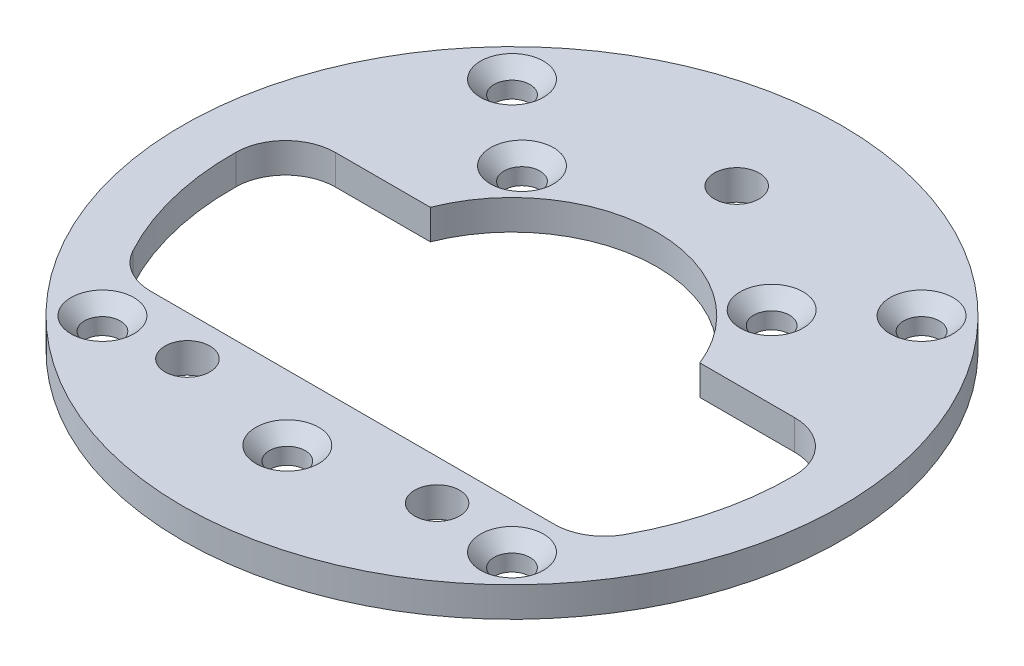
SolidWorks part; units mm, degrees
material "ABS"
ref_plane "Front Plane" through (0, 0, 0) normal (0, 0, 1) x (1, 0, 0)
ref_plane "Top Plane" through (0, 0, 0) normal (0, 1, 0) x (1, 0, 0)
ref_plane "Right Plane" through (0, 0, 0) normal (1, 0, 0) x (0, 0, -1)
sketch "Sketch1" plane through (0, 0, 0) normal (0, 1, 0) x (1, 0, 0)
  circle A0 centre (0, 0) radius 33
  circle A1 centre (0, 0) radius 28
  dimension "D1" = 66
  dimension "D2" = 5
extrude "Boss-Extrude1" add sketch "Sketch1" along normal blind 3
sketch "Sketch2" plane through (0, 3, 0) normal (0, 1, 0) x (1, 0, 0)
  line L0 (-23, -15.9687) -> (23, -15.9687)
  line L1 (-27.4911, 5.3142) -> (-13.4911, 5.3142)
  line L2 (0, 0) -> (7.7557, 0) construction
  line L3 (13.4911, 5.3142) -> (27.4911, 5.3142)
  line L4 (-20.5061, 20.5061) -> (0, 0) construction
  line L5 (-12.5, 13.5) -> (12.5, 13.5) construction
  circle A0 centre (0, 22.5) radius 2.25 construction
  circle A1 centre (-12.5, -20) radius 2.25 construction
  circle A2 centre (12.5, -20) radius 2.25 construction
  circle A4 centre (-12.5, 13.5) radius 1.5
  circle A6 centre (0, 0) radius 28 construction
  arc A8 (-13.4911, 5.3142) -> (13.4911, 5.3142) centre (0, 0) cw
  arc A9 (27.4911, 5.3142) -> (-27.4911, 5.3142) centre (0, 0) ccw
  arc A10 (23, -15.9687) -> (-23, -15.9687) centre (0, 0) cw
  circle A11 centre (12.5, 13.5) radius 1.5
  circle A12 centre (0, 0) radius 29 construction
  circle A13 centre (0, 0) radius 33 construction
  circle A14 centre (-20.5061, 20.5061) radius 1.75 construction
  circle A15 centre (20.5061, 20.5061) radius 1.75 construction
  circle A16 centre (20.5061, -20.5061) radius 1.75 construction
  circle A17 centre (-20.5061, -20.5061) radius 1.75 construction
  circle A18 centre (0, -22.5) radius 1.5
  point P15 (0, 13.5)
  point P19 (0, 0)
  point P44 (0, 0)
  circle M2 centre (0, 0) radius 28
  dimension "D5" = 4.5
  dimension "D6" = 4.5
  dimension "D7" = 4.5
  dimension "D12" = 14.5
  dimension "D16" = 3.5
  dimension "D11" = 3
  dimension "D1" = 25
  dimension "D2" = 12.5
  dimension "D3" = 22.5
  dimension "D4" = 20
  dimension "D14" = 4
  dimension "D15" = 135
  dimension "D8" = 14
  dimension "D9" = 14
  dimension "D10" = 46
  dimension "D13" = 36
  dimension "D18" = 25
  dimension "D19" = 22.5
  dimension "D17" = 4
extrude "Saliente-Extruir1" add sketch "Sketch2" against normal up to surface (3 mm away) contours L1 A8 L3 M2 | L0 M2 region at (0, 3, 20.8526) region at (0, 3, -16.2061) up to face at (0, 0, 33)
sketch "Croquis1" plane through (0, 3, 0) normal (0, 1, 0) x (1, 0, 0)
  circle A0 centre (-20.5061, 20.5061) radius 1.75 construction
  circle A1 centre (-20.5061, 20.5061) radius 1.75
  circle A2 centre (0, 22.5) radius 2.25 construction
  circle A3 centre (0, 22.5) radius 2.25
  circle A4 centre (20.5061, 20.5061) radius 1.75 construction
  circle A5 centre (20.5061, 20.5061) radius 1.75
  circle A12 centre (12.5, -20) radius 2.25 construction
  circle A13 centre (12.5, -20) radius 2.25
  circle A14 centre (-12.5, -20) radius 2.25 construction
  circle A15 centre (-12.5, -20) radius 2.25
  circle A16 centre (-20.5061, -20.5061) radius 1.75 construction
  circle A17 centre (-20.5061, -20.5061) radius 1.75
  circle A18 centre (20.5061, -20.5061) radius 1.75 construction
  circle A19 centre (20.5061, -20.5061) radius 1.75
extrude "Cortar-Extruir1" cut sketch "Croquis1" against normal up to next
hole_wizard "CSK for M3 Flat Head Machine Screw1" positions "Sketch4" profile "Sketch5" countersink size "M3" standard "ANSI Metric" end condition through all
sketch "Sketch4" plane through (0, 3, 0) normal (0, 1, 0) x (1, 0, 0)
  point P0 (-20.5061, 20.5061)
  point P3 (20.5061, 20.5061)
  point P6 (20.5061, -20.5061)
  point P9 (-20.5061, -20.5061)
sketch "Sketch5" plane through (-20.5061, 3, -20.5061) normal (1, 0, 0) x (0, 0, 1)
  line L0 (0, 0) -> (0, 3)
  line L1 (0, 3) -> (1.8, 3)
  line L2 (1.8, 3) -> (1.8, 1.35)
  line L3 (1.8, 1.35) -> (3.15, 0)
  line L5 (3.15, 0) -> (0, 0)
  line L6 (-1.8, 1.35) -> (-3.15, 0) construction
  line L11 (0, -6.35) -> (0, 107.95) construction
  dimension "Thru Hole Dia." = 3.6
  dimension "Thru Hole Depth" = 3
  dimension "Near C'Sink Dia." = 6.3
  dimension "Near C'Sink Angle" = 90
hole_wizard "CSK for M3 Flat Head Machine Screw2" positions "Sketch6" profile "Sketch7" countersink size "M3" standard "ANSI Metric" end condition through all
sketch "Sketch6" plane through (0, 3, 0) normal (0, 1, 0) x (1, 0, 0)
  point P12 (-12.5, 13.5)
  point P15 (12.5, 13.5)
  point P18 (0, -22.5)
sketch "Sketch7" plane through (-12.5, 3, -13.5) normal (1, 0, 0) x (0, 0, 1)
  line L0 (0, 0) -> (0, 3)
  line L1 (0, 3) -> (1.8, 3)
  line L2 (1.8, 3) -> (1.8, 1.35)
  line L3 (1.8, 1.35) -> (3.15, 0)
  line L5 (3.15, 0) -> (0, 0)
  line L6 (-1.8, 1.35) -> (-3.15, 0) construction
  line L11 (0, -6.35) -> (0, 107.95) construction
  dimension "Thru Hole Dia." = 3.6
  dimension "Thru Hole Depth" = 3
  dimension "Near C'Sink Dia." = 6.3
  dimension "Near C'Sink Angle" = 90
fillet "Fillet1" radius 5 4 edges at (-27.4911, 1.5, -5.3142) (27.4911, 1.5, -5.3142) (23, 1.5, 15.9687) (-23, 1.5, 15.9687)
equation "\"D2@Sketch2\"=\"D1@Sketch2\"/2"
equation "\"D6@Sketch2\"=\"D5@Sketch2\""
equation "\"D7@Sketch2\"=\"D6@Sketch2\""
